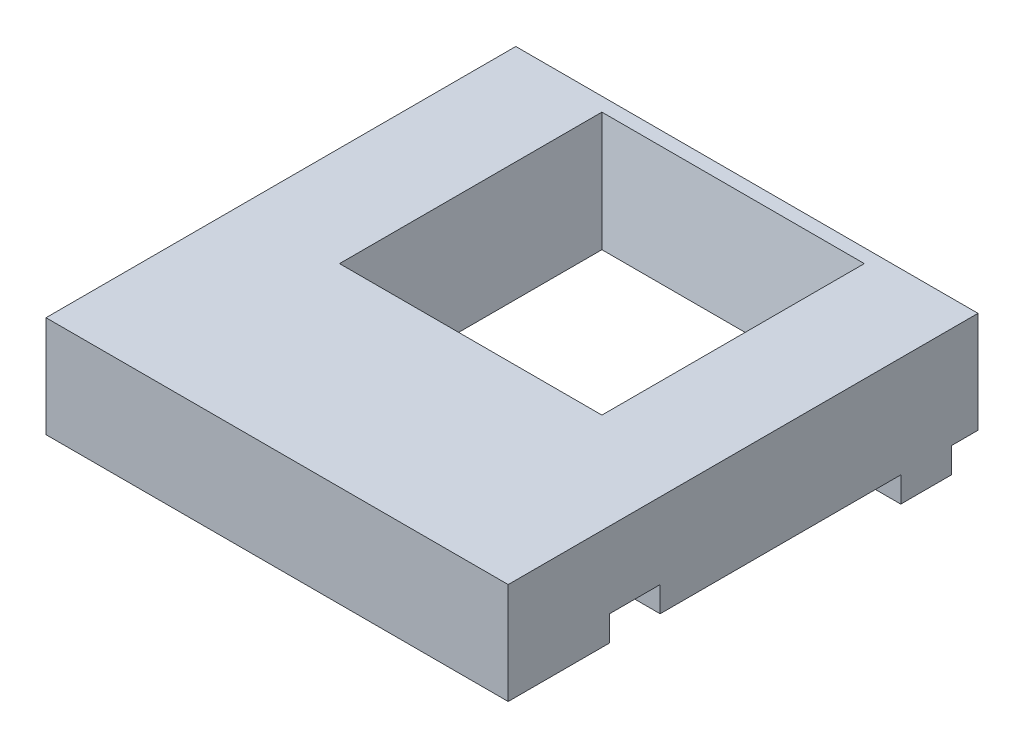
SolidWorks part; units mm, degrees
ref_plane "Front Plane" through (0, 0, 0) normal (0, 0, 1) x (1, 0, 0)
ref_plane "Top Plane" through (0, 0, 0) normal (0, 1, 0) x (1, 0, 0)
ref_plane "Right Plane" through (0, 0, 0) normal (1, 0, 0) x (0, 0, -1)
sketch "Sketch1" plane through (0, 0, 0) normal (0, 1, 0) x (1, 0, 0)
  line L1 (0, 0) -> (36.5, 0)
  line L2 (0, 0) -> (0, -37.1)
  line L3 (0, -37.1) -> (36.5, -37.1)
  line L4 (36.5, 0) -> (36.5, -37.1)
  dimension "D1" = 37.1
  dimension "D2" = 36.5
extrude "Body" add sketch "Sketch1" along normal blind 8
sketch "Sketch2" plane through (0, 0, 0) normal (0, -1, 0) x (-1, 0, 0)
  line L0 (-36.5, 0) -> (0, 0) construction
  line L1 (0, -6.1) -> (-2, -6.1)
  line L2 (0, -6.1) -> (0, -2.1)
  line L3 (0, -2.1) -> (-2, -2.1)
  line L4 (-2, -6.1) -> (-2, -2.1)
  line L5 (-34.5, -29.1) -> (-36.5, -29.1)
  line L6 (-34.5, -29.1) -> (-34.5, -25.1)
  line L7 (-34.5, -25.1) -> (-36.5, -25.1)
  line L8 (-36.5, -29.1) -> (-36.5, -25.1)
  line L10 (0, 0) -> (0, -37.1) construction
  line L11 (0, -37.1) -> (-36.5, -37.1) construction
  line L13 (-36.5, -37.1) -> (-36.5, 0) construction
  point P10 (-1, -2.1)
  dimension "D1" = 2.1
  dimension "D2" = 4
  dimension "D3" = 2
  dimension "D4" = 8
  dimension "D5" = 4
  dimension "D6" = 2
extrude "Female Tabs" cut sketch "Sketch2" against normal blind 2
sketch "Sketch3" plane through (0, 0, 0) normal (0, -1, 0) x (-1, 0, 0)
  line L0 (-36.5, -29.1) -> (-34.5, -29.1) construction
  line L1 (0, -29.1) -> (-2, -29.1)
  line L2 (0, -29.1) -> (0, -25.1)
  line L3 (0, -25.1) -> (-2, -25.1)
  line L4 (-2, -29.1) -> (-2, -25.1)
  line L5 (-34.5, -6.1) -> (-36.5, -6.1)
  line L6 (-34.5, -6.1) -> (-34.5, -2.1)
  line L7 (-34.5, -2.1) -> (-36.5, -2.1)
  line L8 (-36.5, -6.1) -> (-36.5, -2.1)
  line L9 (0, -6.1) -> (0, -37.1) construction
  line L10 (-36.5, -25.1) -> (-36.5, 0) construction
  line L11 (0, -2.1) -> (-2, -2.1) construction
  line L12 (-36.5, 0) -> (0, 0) construction
  dimension "D1" = 2
  dimension "D2" = 4
  dimension "D3" = 2
  dimension "D4" = 4
extrude "Male Tabs" add sketch "Sketch3" along normal blind 2
sketch "Sketch5" plane through (0, 0, 0) normal (0, -1, 0) x (-1, 0, 0)
  line L0 (-36.5, 0) -> (0, 0) construction
  line L1 (-27.2, -2.5) -> (-9.3, -2.5)
  line L2 (-27.2, -2.5) -> (-27.2, -20.4)
  line L3 (-27.2, -20.4) -> (-9.3, -20.4)
  line L4 (-9.3, -2.5) -> (-9.3, -20.4)
  line L5 (-36.5, -2.1) -> (-36.5, 0) construction
  line L6 (0, -6.1) -> (0, -25.1) construction
  line L7 (0, -37.1) -> (-36.5, -37.1) construction
  dimension "D1" = 2.5
  dimension "D2" = 9.3
  dimension "D3" = 9.3
  dimension "D4" = 16.7
extrude "SiPM Window" cut sketch "Sketch5" against normal up to next (8 mm away) draft 10 draft outward yes
sketch "Sketch6" plane through (0, 0, 0) normal (0, -1, 0) x (1, 0, 0)
  line L0 (36.5, 0) -> (0, 0) construction
  line L1 (34, 1.5) -> (29.2, 1.5)
  line L2 (34, 1.5) -> (34, 35.1)
  line L4 (29.2, 1.5) -> (29.2, 22.4)
  line L5 (29.2, 22.4) -> (7.3, 22.4)
  line L9 (7.3, 1.5) -> (2.5, 1.5)
  line L10 (7.3, 1.5) -> (7.3, 22.4)
  line L13 (36.5, 25.1) -> (36.5, 6.1) construction
  line L16 (34, 35.1) -> (2.5, 35.1)
  line L17 (2.5, 35.1) -> (2.5, 1.5)
  line L18 (0, 6.1) -> (0, 25.1) construction
  line L19 (0, 37.1) -> (36.5, 37.1) construction
  line L20 (27.2, 20.4) -> (9.3, 20.4) construction
  line L21 (9.3, 20.4) -> (9.3, 2.5) construction
  line L22 (27.2, 2.5) -> (27.2, 20.4) construction
  dimension "D1" = 1.5
  dimension "D2" = 1.5
  dimension "D3" = 2.5
  dimension "D4" = 2.5
  dimension "D5" = 2
  dimension "D6" = 2
  dimension "D7" = 2
  dimension "D8" = 2
extrude "Cut-Extrude2" cut sketch "Sketch6" against normal offset from surface (6 mm away) 2 up to face at (18.25, 8, 11.45)
